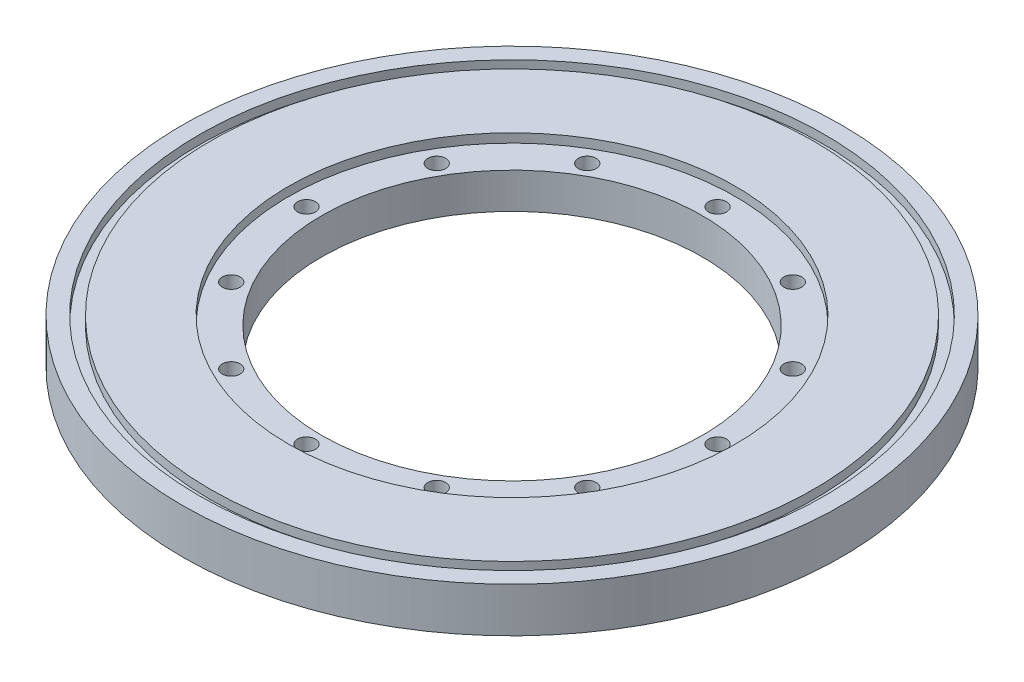
SolidWorks part; units mm, degrees
ref_plane "Front Plane" through (0, 0, 0) normal (0, 0, 1) x (1, 0, 0)
ref_plane "Top Plane" through (0, 0, 0) normal (0, 1, 0) x (1, 0, 0)
ref_plane "Right Plane" through (0, 0, 0) normal (1, 0, 0) x (0, 0, -1)
sketch "Sketch1" plane through (0, 0, 0) normal (0, 1, 0) x (1, 0, 0)
  circle A0 centre (0, 0) radius 93.6625
  dimension "D1" = 187.325
extrude "Boss-Extrude1" add sketch "Sketch1" along normal blind 12.7
sketch "Sketch2" plane through (0, 12.7, 0) normal (0, 1, 0) x (1, 0, 0)
  circle A0 centre (0, 0) radius 54.102
  dimension "D1" = 108.204
extrude "Cut-Extrude1" cut sketch "Sketch2" against normal through all
sketch "Sketch3" plane through (0, 12.7, 0) normal (0, 1, 0) x (1, 0, 0)
  circle A0 centre (0, 0) radius 63.5
  dimension "D1" = 127
extrude "Cut-Extrude2" cut sketch "Sketch3" against normal blind 2.54
sketch "Sketch4" plane through (0, 12.7, 0) normal (0, 1, 0) x (1, 0, 0)
  circle A0 centre (0, 58.42) radius 2.54
  dimension "D1" = 5.08
  dimension "D2" = 58.42
extrude "Cut-Extrude3" cut sketch "Sketch4" against normal through all
pattern_circular "CirPattern1" count 12 over 360 about axis through (0, 12.7, 0) along (0, 1, 0) of "Cut-Extrude3"
sketch "Sketch5" plane through (0, 12.7, 0) normal (0, 1, 0) x (1, 0, 0)
  circle A0 centre (0, 0) radius 85.725
  circle A1 centre (0, 0) radius 88.9
  dimension "D1" = 171.45
  dimension "D2" = 177.8
extrude "Cut-Extrude4" cut sketch "Sketch5" against normal blind 2.54
